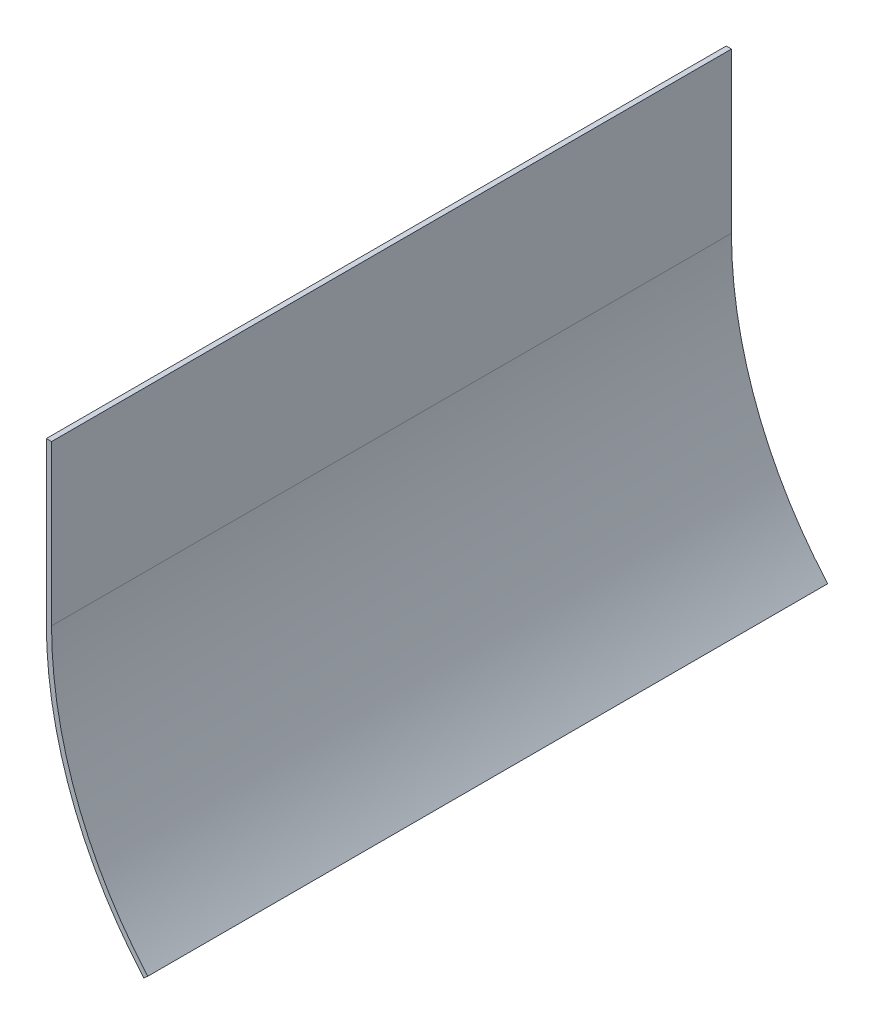
SolidWorks part; units mm, degrees
ref_plane "Front Plane" through (0, 0, 0) normal (0, 0, 1) x (1, 0, 0)
ref_plane "Top Plane" through (0, 0, 0) normal (0, 1, 0) x (1, 0, 0)
ref_plane "Right Plane" through (0, 0, 0) normal (1, 0, 0) x (0, 0, -1)
sketch "Sketch1" plane through (0, 0, 0) normal (0, 0, 1) x (1, 0, 0)
  line L2 (812.5417, 1387.3698) -> (812.5417, 1484.2708)
  line L4 (815.7167, 1387.3698) -> (815.7167, 1484.2708)
  line L5 (812.5417, 1484.2708) -> (815.7167, 1484.2708)
  line L6 (874.1429, 1232.3666) -> (871.7578, 1230.2708)
  arc A0 (812.5417, 1387.3698) -> (871.7578, 1230.2708) centre (1050.5397, 1387.3698) ccw
  arc A1 (815.7167, 1387.3698) -> (874.1429, 1232.3666) centre (1050.5397, 1387.3698) ccw
  dimension "D1" = 237.998
  dimension "D3" = 237.998
  dimension "D4" = 3.175
extrude "Boss-Extrude1" add sketch "Sketch1" along normal blind 412.75
